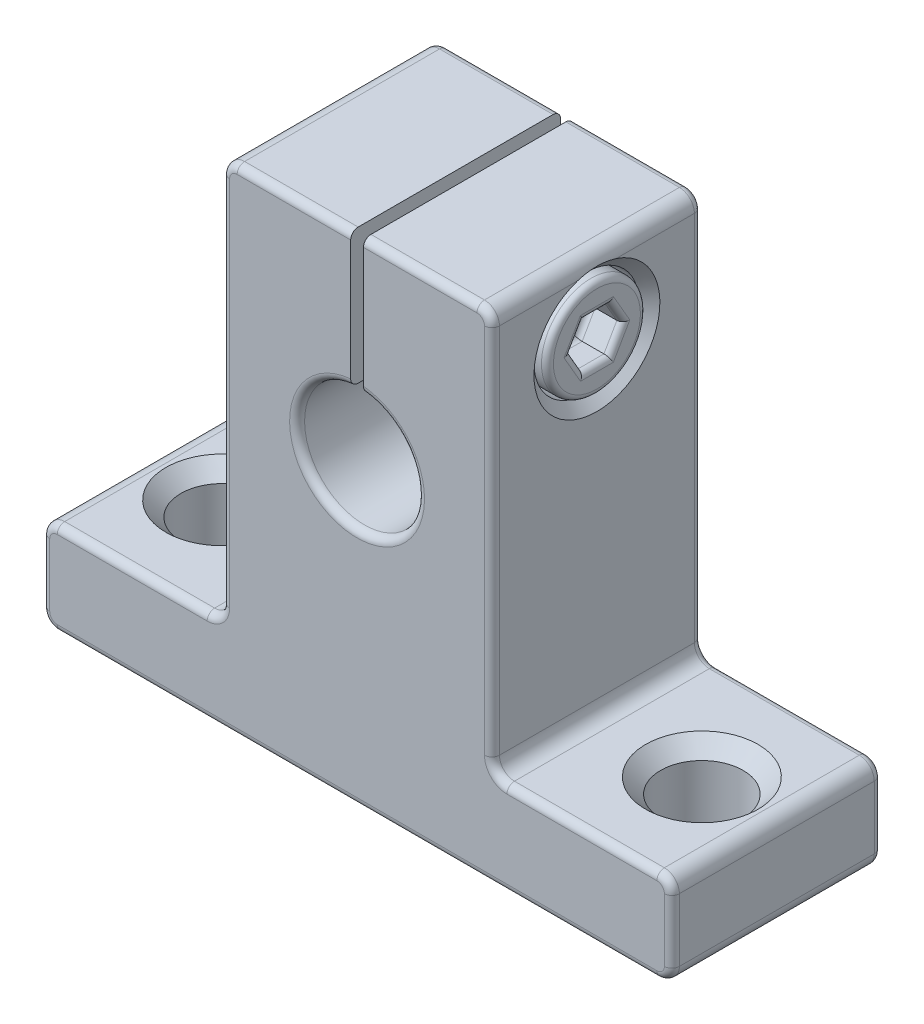
SolidWorks part; units mm, degrees
ref_plane "Front Plane" through (0, 0, 0) normal (0, 0, 1) x (1, 0, 0)
ref_plane "Top Plane" through (0, 0, 0) normal (0, 1, 0) x (1, 0, 0)
ref_plane "Right Plane" through (0, 0, 0) normal (1, 0, 0) x (0, 0, -1)
sketch "Sketch1" plane through (0, 0, 0) normal (0, 0, 1) x (1, 0, 0)
  line L0 (-21, 6.2) -> (-21, 0)
  line L1 (-21, 0) -> (21, 0)
  line L3 (9, 33) -> (-9, 33)
  line L4 (-9, 33) -> (-9, 6.2)
  line L5 (-9, 6.2) -> (-21, 6.2)
  line L6 (0, 33) -> (0, 0) construction
  line L7 (9, 6.2) -> (21, 6.2)
  line L8 (9, 33) -> (9, 6.2)
  line L9 (21, 6.2) -> (21, 0)
  dimension "D1" = 18
  dimension "D2" = 42
  dimension "D3" = 6.2
  dimension "D4" = 33
extrude "Boss-Extrude1" add sketch "Sketch1" along normal blind 14
sketch "Sketch2" plane through (0, 0, 14) normal (0, 0, 1) x (1, 0, 0)
  line L0 (-21, 0) -> (21, 0) construction
  line L1 (-0.426, 23.9773) -> (-0.426, 33)
  line L2 (9, 33) -> (-9, 33) construction
  line L3 (0, -7.7) -> (0, 7.7) construction
  line L4 (0.426, 23.9773) -> (0.426, 33)
  line L5 (-0.426, 33) -> (0.426, 33)
  arc A0 (-0.426, 23.9773) -> (0.426, 23.9773) centre (0, 20) ccw
  dimension "D2" = 8
  dimension "D1" = 20
extrude "Cut-Extrude1" cut sketch "Sketch2" against normal through all
sketch "Sketch3" plane through (0, 0, 0) normal (0, -1, 0) x (1, 0, 0)
  line L0 (-21, 14) -> (-21, 0) construction
  line L1 (0, 0) -> (0, 14) construction
  line L2 (-21, 14) -> (21, 14) construction
  circle A0 centre (-16, 7) radius 2.75
  circle A1 centre (16, 7) radius 2.75
  point P5 (-21, 7)
  dimension "D1" = 5.5
  dimension "D2" = 32
extrude "Cut-Extrude2" cut sketch "Sketch3" against normal up to surface (6.2 mm away) up to face at (-15, 6.2, 7)
sketch "Sketch5" plane through (9, 0, 0) normal (1, 0, 0) x (0, 0, -1)
  line L0 (-14, 33) -> (0, 33) construction
  circle A0 centre (-7, 28) radius 3.5
  point P5 (-7, 33)
  dimension "D1" = 7
  dimension "D2" = 5
extrude "Cut-Extrude3" cut sketch "Sketch5" against normal blind 4.5
sketch "Sketch6" plane through (4.5, 0, 0) normal (1, 0, 0) x (0, 0, -1)
  circle A0 centre (-7, 28) radius 2
  dimension "D1" = 4
extrude "Cut-Extrude4" cut sketch "Sketch6" against normal through all
chamfer "Chamfer1" distance 1 angle 45 4 edges at (13.25, 0, 7) (-13.25, 0, 7) (18.75, 6.2, 7) (-13.25, 6.2, 7)
chamfer "Chamfer2" distance 1.5 angle 45 1 edges at (-9, 30, 7)
chamfer "Chamfer3" distance 0.7 angle 45 1 edges at (9, 31.5, 7)
fillet "Fillet1" radius 1 8 edges at (-21, 0, 7) (-21, 6.2, 7) (-9, 6.2, 7) (21, 0, 7) (21, 6.2, 7) (9, 6.2, 7) (-9, 33, 7) (9, 33, 7)
fillet "Fillet2" radius 0.5 36 edges at (4.213, 33, 0) (8.7071, 32.7071, 0) (9, 19.6, 0) (9.2929, 6.4929, 0) (15, 6.2, 0) (20.7071, 5.9071, 0) (21, 3.1, 0) (20.7071, 0.2929, 0) (0, 0, 0) (-20.7071, 0.2929, 0) (-21, 3.1, 0) (-20.7071, 5.9071, 0) (-15, 6.2, 0) (-9.2929, 6.4929, 0) (-9, 19.6, 0) (-8.7071, 32.7071, 0) (4.213, 33, 14) (8.7071, 32.7071, 14) (9, 19.6, 14) (9.2929, 6.4929, 14) (15, 6.2, 14) (20.7071, 5.9071, 14) (21, 3.1, 14) (20.7071, 0.2929, 14) (0, 0, 14) (-20.7071, 0.2929, 14) (-21, 3.1, 14) (-20.7071, 5.9071, 14) (-15, 6.2, 14) (-9.2929, 6.4929, 14) (-9, 19.6, 14) (-8.7071, 32.7071, 14) (0, 16, 0) (-4.213, 33, 0) (0, 16, 14) (-4.213, 33, 14)
sketch "Sketch7" plane through (4.5, 0, 0) normal (1, 0, 0) x (0, 0, -1)
  circle A2 centre (-7, 28) radius 3.3
  circle A3 centre (-7, 28) radius 3.3
  dimension "D1" = 0.2
extrude "Boss-Extrude2" add sketch "Sketch7" along normal up to surface (4.5 mm away) separate body up to face at (9, 22.3667, 7)
sketch "Sketch8" plane through (4.5, 0, 0) normal (-1, 0, 0) x (0, 0, 1)
  circle A2 centre (7, 28) radius 1.8
  circle A3 centre (7, 28) radius 1.8
  dimension "D1" = 0.2
extrude "Boss-Extrude3" add sketch "Sketch8" along normal blind 12
sketch "Sketch9" plane through (9, 0, 0) normal (1, 0, 0) x (0, 0, -1)
  line L1 (-7.866, 29.5) -> (-8.7321, 28)
  line L2 (-8.7321, 28) -> (-7.866, 26.5)
  line L3 (-7.866, 26.5) -> (-6.134, 26.5)
  line L4 (-6.134, 26.5) -> (-5.2679, 28)
  line L5 (-5.2679, 28) -> (-6.134, 29.5)
  line L6 (-6.134, 29.5) -> (-7.866, 29.5)
  circle A0 centre (-7, 28) radius 1.5 construction
  dimension "D1" = 3
extrude "Cut-Extrude5" cut sketch "Sketch9" against normal blind 2.25
fillet "Fillet3" radius 0.4 13 edges at (9, 24.7, 7) (9, 27.25, 8.299) (9, 26.5, 7) (9, 27.25, 5.701) (9, 28.75, 5.701) (9, 29.5, 7) (9, 28.75, 8.299) (6.75, 28.75, 5.701) (6.75, 27.25, 5.701) (6.75, 26.5, 7) (6.75, 27.25, 8.299) (6.75, 28.75, 8.299) (6.75, 29.5, 7)
